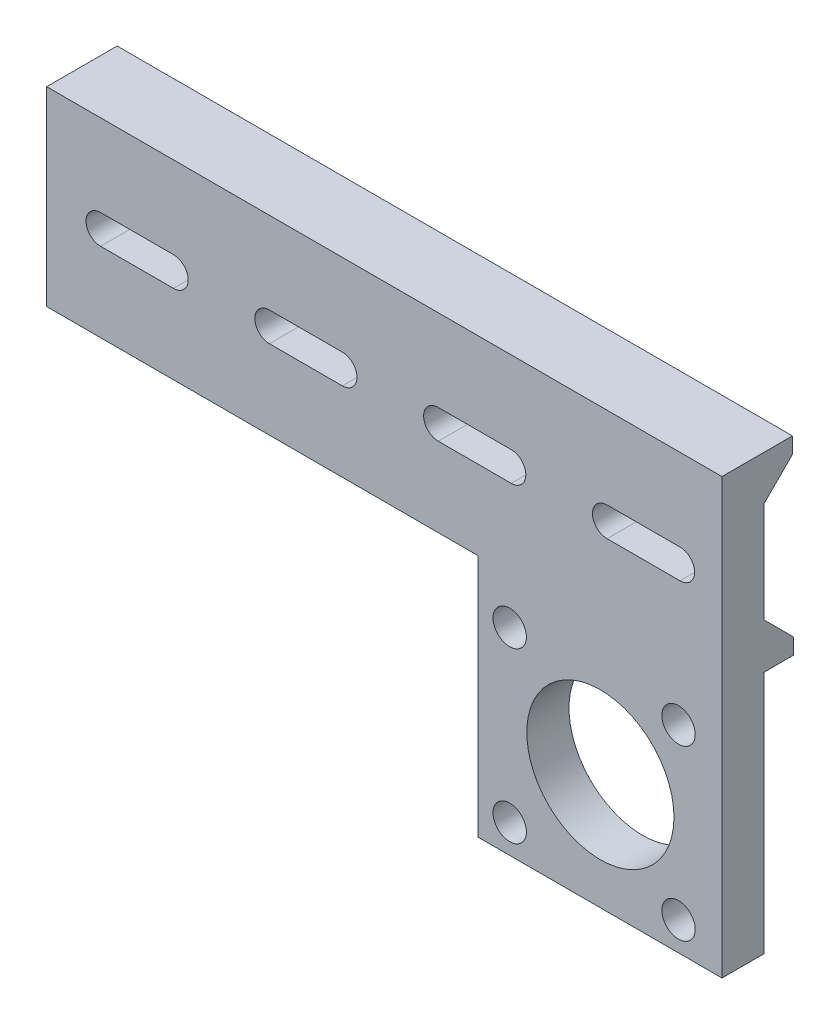
SolidWorks part; units mm, degrees
ref_plane "Front Plane" through (0, 0, 0) normal (0, 0, 1) x (1, 0, 0)
ref_plane "Top Plane" through (0, 0, 0) normal (0, 1, 0) x (1, 0, 0)
ref_plane "Right Plane" through (0, 0, 0) normal (1, 0, 0) x (0, 0, -1)
sketch "Sketch2" plane through (0, 0, 40) normal (0, 0, 1) x (1, 0, 0)
  line L1 (-58.4044, 35.4344) -> (-0.5627, 35.4344)
  line L2 (-58.4044, 35.4344) -> (-58.4044, -22.3289)
  line L3 (-58.4044, -22.3289) -> (-0.5627, -22.3289)
  line L4 (-0.5627, 35.4344) -> (-0.5627, -22.3289)
extrude "Boss-Extrude2" add sketch "Sketch2" along normal blind 10
sketch "Sketch3" plane through (0, 0, 50) normal (0, 0, 1) x (1, 0, 0)
  circle A0 centre (-29.3755, 4.9656) radius 17.4379
extrude "Cut-Extrude1" cut sketch "Sketch3" against normal blind 10
sketch "Sketch4" plane through (0, 0, 50) normal (0, 0, 1) x (1, 0, 0)
  circle A0 centre (-50.8631, -15.5453) radius 3.9557
extrude "Cut-Extrude2" cut sketch "Sketch4" against normal blind 10
pattern_linear "LPattern1" count 2 spacing 40 along (0, 1, 0) count 2 spacing 40 along (1, 0, 0) of "Cut-Extrude2"
sketch "Sketch6" plane through (-0.5627, 0, 0) normal (1, 0, 0) x (0, 0, -1)
  line L0 (-50, 35.4344) -> (-33.1047, 35.4344)
  line L1 (-33.1047, 35.4344) -> (-33.1047, 39.2329)
  line L2 (-33.1047, 39.2329) -> (-40, 46.1282)
  line L3 (-40, 46.1282) -> (-40, 70.0722)
  line L4 (-40, 70.0722) -> (-33.3087, 76.7636)
  line L5 (-33.3087, 76.7636) -> (-33.3087, 80.5621)
  line L6 (-33.3087, 80.5621) -> (-50, 80.5621)
  line L7 (-50, 80.5621) -> (-50, 35.4344)
  dimension "D1" = 10
extrude "Boss-Extrude3" add sketch "Sketch6" against normal blind 160
sketch "Sketch7" plane through (0, 0, 50) normal (0, 0, 1) x (1, 0, 0)
  line L0 (-147.7937, 57.6608) -> (-130.5058, 57.6608) construction
  line L1 (-147.7937, 61.1224) -> (-130.5058, 61.1224)
  line L2 (-147.7937, 54.1992) -> (-130.5058, 54.1992)
  arc A0 (-147.7937, 61.1224) -> (-147.7937, 54.1992) centre (-147.7937, 57.6608) ccw
  arc A1 (-130.5058, 54.1992) -> (-130.5058, 61.1224) centre (-130.5058, 57.6608) ccw
  point P2 (-139.1497, 57.6608)
  point P7 (-147.7937, 57.1273)
  point P8 (-130.5058, 57.6608)
extrude "Cut-Extrude4" cut sketch "Sketch7" against normal blind 140
pattern_linear "LPattern3" count 4 spacing 40 along (1, 0, 0) of "Cut-Extrude4"
